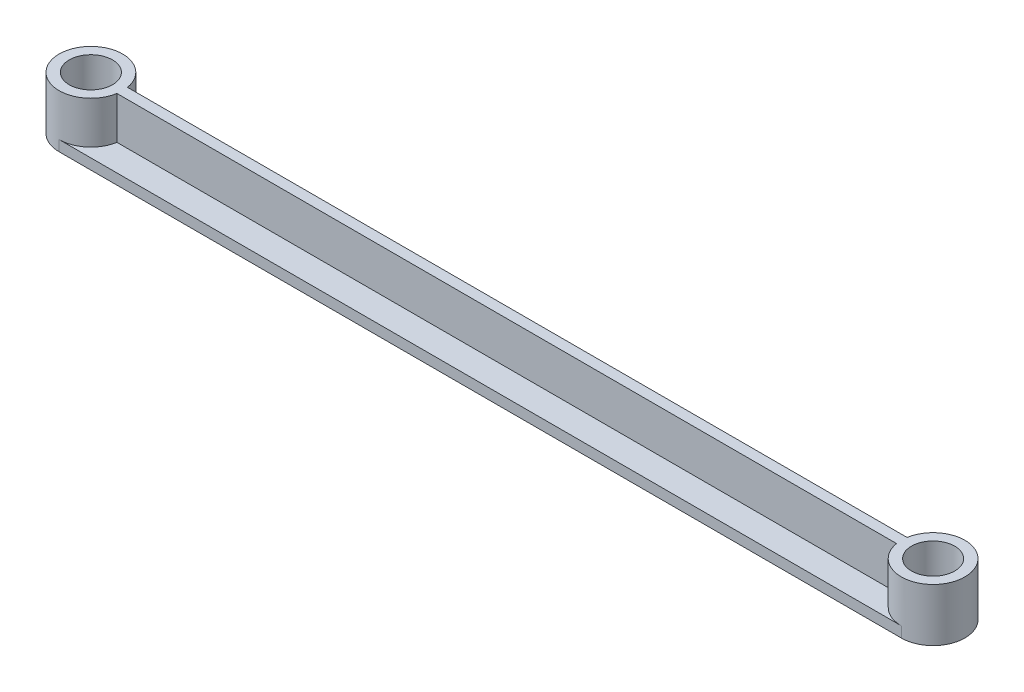
SolidWorks part; units mm, degrees
ref_plane "Front Plane" through (0, 0, 0) normal (0, 0, 1) x (1, 0, 0)
ref_plane "Top Plane" through (0, 0, 0) normal (0, 1, 0) x (1, 0, 0)
ref_plane "Right Plane" through (0, 0, 0) normal (1, 0, 0) x (0, 0, -1)
sketch "Sketch1" plane through (0, 0, 0) normal (0, 1, 0) x (1, 0, 0)
  line L0 (0, 0) -> (-126.2507, 0) construction
  line L1 (0, -4.7625) -> (-126.2507, -4.7625)
  line L2 (0, 4.7625) -> (-126.2507, 4.7625)
  arc A0 (0, -4.7625) -> (0, 4.7625) centre (0, 0) ccw
  arc A1 (-126.2507, 4.7625) -> (-126.2507, -4.7625) centre (-126.2507, 0) ccw
  point P3 (-63.1253, 0)
  dimension "D1" = 4.7625
  dimension "D2" = 126.2507
extrude "Boss-Extrude1" add sketch "Sketch1" along normal blind 1.5875
sketch "Sketch2" plane through (0, 1.5875, 0) normal (0, 1, 0) x (1, 0, 0)
  circle A0 centre (-126.2507, 0) radius 4.7625
  circle A1 centre (0, 0) radius 4.7625
  circle A2 centre (-126.2507, 0) radius 3.2385
  circle A3 centre (0, 0) radius 3.2385
  dimension "D1" = 6.477
  dimension "D2" = 6.477
extrude "Boss-Extrude2" add sketch "Sketch2" along normal blind 6.35
sketch "Sketch3" plane through (0, 0, 0) normal (1, 0, 0) x (0, 0, -1)
  line L0 (4.7625, 1.5875) -> (-4.7625, 1.5875) construction
  line L1 (-0.7937, 7.9375) -> (0.7937, 7.9375)
  line L2 (-0.7937, 7.9375) -> (-0.7938, 1.5875)
  line L3 (-0.7938, 1.5875) -> (0.7938, 1.5875)
  line L4 (0.7937, 7.9375) -> (0.7938, 1.5875)
  line L5 (0, 0) -> (0, 1.5875) construction
  dimension "D1" = 1.5875
  dimension "D2" = 6.35
extrude "Boss-Extrude3" add sketch "Sketch3" along normal up to next and the other way up to next from offset 25.4 offset against normal yes
